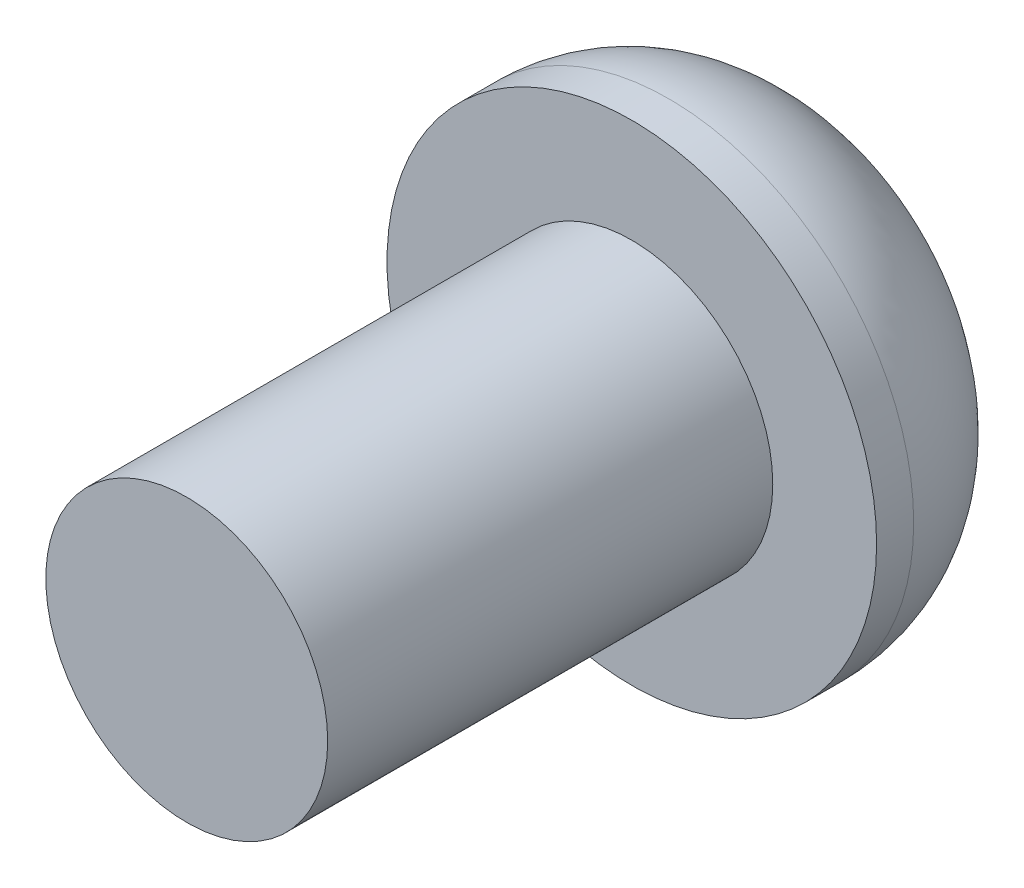
SolidWorks part; units mm, degrees
ref_plane "Front Plane" through (0, 0, 0) normal (0, 0, 1) x (1, 0, 0)
ref_plane "Top Plane" through (0, 0, 0) normal (0, 1, 0) x (1, 0, 0)
ref_plane "Right Plane" through (0, 0, 0) normal (1, 0, 0) x (0, 0, -1)
sketch "Sketch1" plane through (0, 0, 0) normal (0, 0, 1) x (1, 0, 0)
  circle A0 centre (0, 0) radius 1.65
  circle A1 centre (0, 0) radius 0.95
  dimension "D1" = 3.3
  dimension "D2" = 1.9
extrude "Boss-Extrude1" add sketch "Sketch1" along normal blind 1.3 contours A1 | A0 A1 region at (-1.6033, 0, 0) region at (0, 0, 0)
extrude "Boss-Extrude2" add sketch "Sketch1<3>" along normal blind 3 from surface contours A1 region at (0, 0, 0) starting at face at (1.65, 0, 1.3)
sketch "Sketch1<3>" plane through (0, 0, 0) normal (0, 0, 1) x (1, 0, 0) same geometry as "Sketch1"
fillet "Fillet1" radius 1.05 1 edges at (1.65, 0, 0)
extrude "Cut-Extrude1" cut sketch "Sketch1<4>" along normal blind 1 contours A1 region at (0, 0, 0)
sketch "Sketch1<4>" plane through (0, 0, 0) normal (0, 0, 1) x (1, 0, 0) same geometry as "Sketch1"
